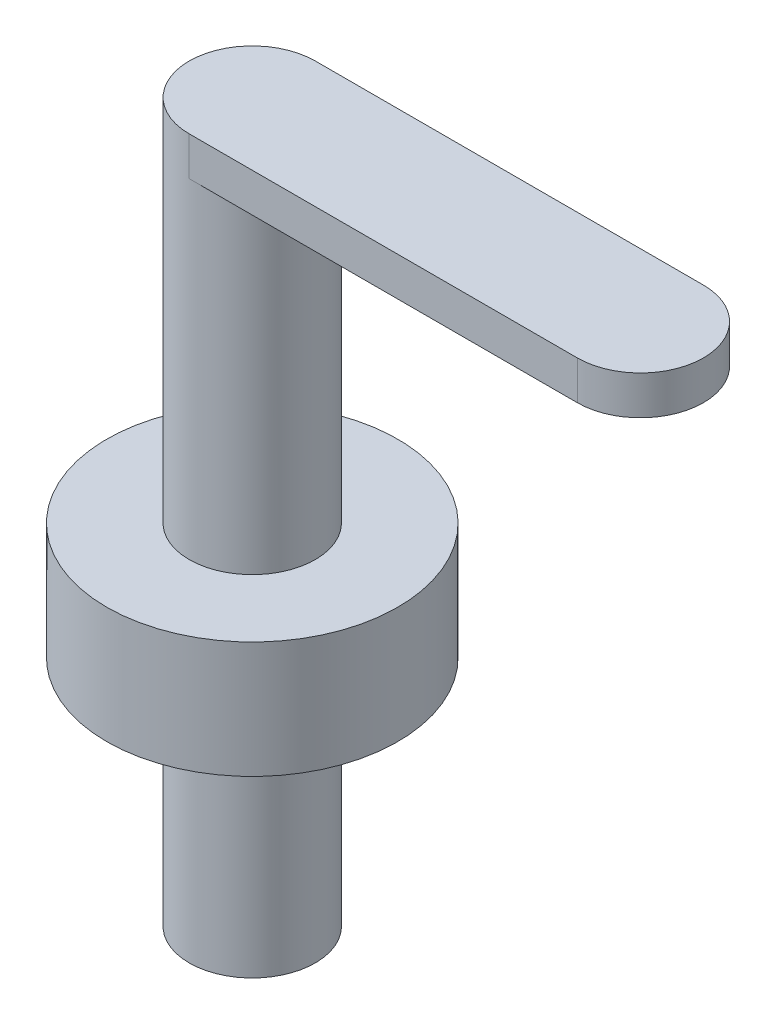
SolidWorks part; units mm, degrees
ref_plane "Alzado" through (0, 0, 0) normal (0, 0, 1) x (1, 0, 0)
ref_plane "Planta" through (0, 0, 0) normal (0, 1, 0) x (1, 0, 0)
ref_plane "Vista lateral" through (0, 0, 0) normal (1, 0, 0) x (0, 0, -1)
sketch "Croquis1" plane through (0, 0, 0) normal (0, 1, 0) x (1, 0, 0)
  line L0 (0, 0) -> (0, 17.5) construction
  circle A0 centre (0, 0) radius 7.5
  circle A1 centre (0, 0) radius 3.25
  circle A2 centre (0, 17.5) radius 10 construction
  dimension "D2" = 6.5
  dimension "D4" = 20
  dimension "D3" = 17.5
extrude "Saliente-Extruir1" add sketch "Croquis1" along normal blind 20 and the other way blind 15 contours A1 region at (0, 0, 0)
extrude "Saliente-Extruir2" add sketch "Croquis1<3>" along normal mid plane 6
sketch "Croquis1<3>" plane through (0, 0, 0) normal (0, 1, 0) x (1, 0, 0) same geometry as "Croquis1"
sketch "Croquis2" plane through (0, 20, 0) normal (0, 1, 0) x (1, 0, 0)
  line L0 (0, 0) -> (20, 0) construction
  line L1 (0, 3.25) -> (20, 3.25)
  line L2 (0, -3.25) -> (20, -3.25)
  arc A0 (0, 3.25) -> (0, -3.25) centre (0, 0) ccw
  arc A1 (20, -3.25) -> (20, 3.25) centre (20, 0) ccw
  circle A2 centre (0, 0) radius 3.25 construction
  point P3 (10, 0)
  dimension "D1" = 20
extrude "Saliente-Extruir3" add sketch "Croquis2" along normal blind 2
